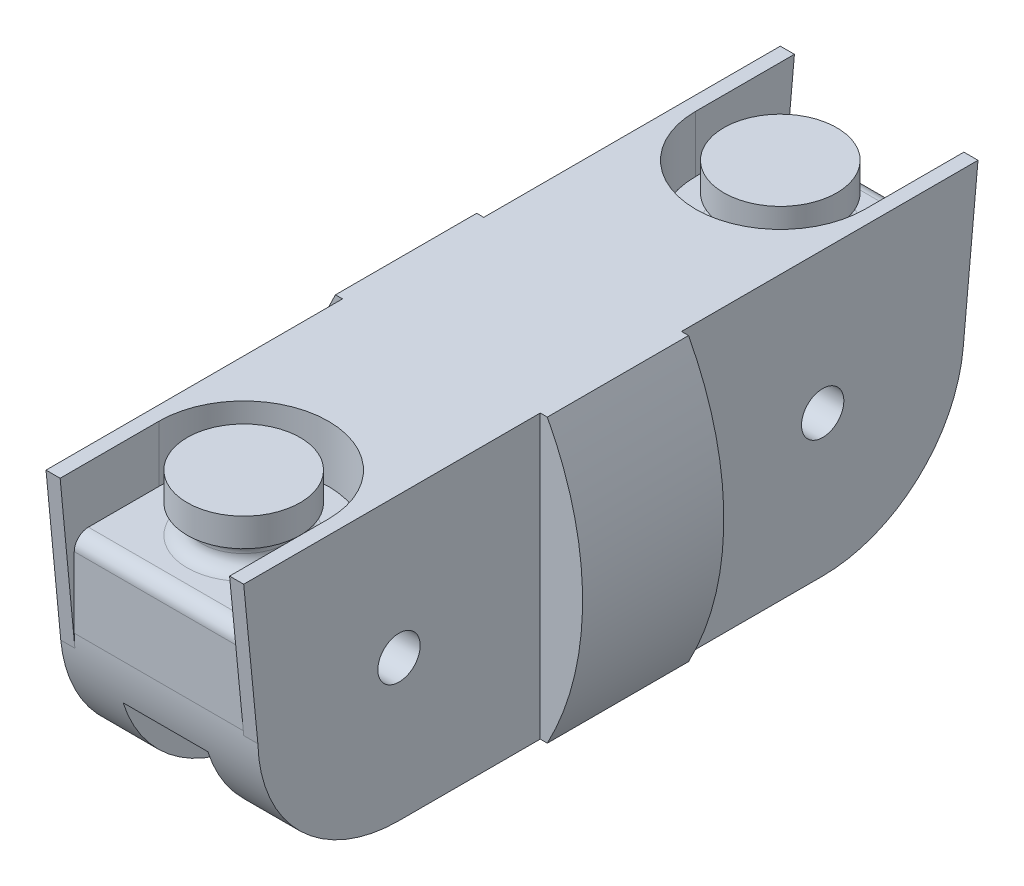
SolidWorks part; units mm, degrees
ref_plane "Alzado" through (0, 0, 0) normal (0, 0, 1) x (1, 0, 0)
ref_plane "Planta" through (0, 0, 0) normal (0, 1, 0) x (1, 0, 0)
ref_plane "Vista lateral" through (0, 0, 0) normal (1, 0, 0) x (0, 0, -1)
sketch "Croquis2" plane through (0, 0, 0) normal (0, 0, 1) x (1, 0, 0)
  line L5 (-7.5, 10) -> (7.5, 10)
  line L7 (-7.5, -10) -> (7.5, -10)
  line L9 (-7.5, 10) -> (7.5, -10) construction
  line L10 (-7.5, -10) -> (7.5, 10) construction
  arc A2 (-7.5, 10) -> (-7.5, -10) centre (11.25, 0) ccw
  arc A3 (7.5, -10) -> (7.5, 10) centre (-11.25, 0) ccw
  point P0 (0, 0)
  dimension "D1" = 15
  dimension "D2" = 20
extrude "Saliente-Extruir1" add sketch "Croquis2" along normal blind 10
sketch "Croquis3" plane through (0, 0, 0) normal (0, 0, -1) x (-1, 0, 0)
  line L0 (7.5, -10) -> (-7.5, -10) construction
  circle A0 centre (0, -7) radius 1.5
  dimension "D2" = 3
  dimension "D1" = 3
extrude "Cortar-Extruir1" cut sketch "Croquis3" against normal blind 10
sketch "Croquis4" plane through (0, 0, 0) normal (0, 0, -1) x (-1, 0, 0)
  line L0 (7.5, -10) -> (-7.5, -10) construction
  line L2 (-7, 10) -> (-7, -10)
  line L3 (-7, -10) -> (-3, -10)
  line L4 (7, 10) -> (7, -10)
  line L5 (-7, 10) -> (7, -10) construction
  line L6 (-7, -10) -> (7, 10) construction
  line L7 (-3, -3) -> (-3, -10)
  line L8 (3, -3) -> (3, -10)
  line L10 (3, -10) -> (7, -10)
  line L11 (-3, -3) -> (3, -3)
  line L13 (-7, 10) -> (7, 10)
  point P0 (0, 0)
  dimension "D1" = 14
  dimension "D2" = 4
  dimension "D3" = 4
  dimension "D4" = 7
extrude "Saliente-Extruir2" add sketch "Croquis4" along normal blind 20
sketch "Croquis5" plane through (0, 0, 10) normal (0, 0, 1) x (1, 0, 0)
  line L0 (-7.5, -10) -> (7.5, -10) construction
  line L2 (-7, 10) -> (-7, -10)
  line L3 (-7, -10) -> (-3, -10)
  line L4 (7, 10) -> (7, -10)
  line L5 (-7, 10) -> (7, -10) construction
  line L6 (-7, -10) -> (7, 10) construction
  line L7 (-3, -3) -> (-3, -10)
  line L8 (3, -3) -> (3, -10)
  line L9 (3, -10) -> (7, -10)
  line L11 (-3, -3) -> (3, -3)
  line L12 (-7, 10) -> (7, 10)
  point P0 (0, 0)
  dimension "D1" = 14
  dimension "D4" = 7
extrude "Saliente-Extruir3" add sketch "Croquis5" along normal blind 20
sketch "Croquis6" plane through (7, 0, 0) normal (1, 0, 0) x (0, 0, -1)
  line L0 (-30, -10) -> (-30, 10) construction
  line L1 (-30, -10) -> (-10, -10) construction
  line L2 (20, 10) -> (20, -10) construction
  circle A0 centre (-20, 0) radius 1.5
  circle A1 centre (10, 0) radius 1.5
  dimension "D3" = 3
  dimension "D6" = 3
  dimension "D1" = 10
  dimension "D2" = 10
  dimension "D4" = 10
extrude "Cortar-Extruir2" cut sketch "Croquis6" against normal blind 14
fillet "Redondeo1" radius 10 4 edges at (5, -10, 30) (-5, -10, 30) (5, -10, -20) (-5, -10, -20)
sketch "Sketch1" plane through (0, 10, 0) normal (0, 1, 0) x (1, 0, 0)
  line L0 (-7, 20) -> (7, 20) construction
  line L1 (7, -30) -> (-7, -30) construction
  line L4 (-6, 14) -> (-6, 20)
  line L5 (-6, 20) -> (6, 20)
  line L6 (6, 14) -> (6, 20)
  line L8 (-6, -24) -> (-6, -30)
  line L9 (-6, -30) -> (6, -30)
  line L10 (6, -24) -> (6, -30)
  arc A0 (-6, 14) -> (6, 14) centre (0, 14) ccw
  arc A1 (6, -24) -> (-6, -24) centre (0, -24) ccw
  dimension "D1" = 12
  dimension "D2" = 12
  dimension "D3" = 6
  dimension "D4" = 6
extrude "Cut-Extrude1" cut sketch "Sketch1" against normal blind 4
sketch "Sketch2" plane through (0, 6, 0) normal (0, 1, 0) x (1, 0, 0)
  line L0 (-6, -30) -> (6, -30) construction
  line L1 (6, 20) -> (-6, 20) construction
  circle A0 centre (0, 14) radius 3
  circle A1 centre (0, -24) radius 3
  dimension "D1" = 6
  dimension "D2" = 6
  dimension "D3" = 6
  dimension "D4" = 6
extrude "Boss-Extrude1" add sketch "Sketch2" along normal blind 2
sketch "Sketch3" plane through (0, 8, 0) normal (0, 1, 0) x (1, 0, 0)
  circle A0 centre (0, -24) radius 4
  circle A1 centre (0, 14) radius 4
  dimension "D1" = 8
  dimension "D2" = 8
extrude "Boss-Extrude2" add sketch "Sketch3" along normal blind 2
fillet "Fillet1" radius 1 4 edges at (0, 8, 27) (0, 6, 27) (0, 8, -11) (0, 6, -11)
fillet "Fillet2" radius 1 2 edges at (0, 6, 30) (0, 6, -20)
fillet "Fillet3" radius 1 2 edges at (-1.5, -7, 0) (-1.5, -7, 10)
sketch "Sketch4" plane through (7, 0, 0) normal (1, 0, 0) x (0, 0, -1)
  line L0 (20, 10) -> (21, 10)
  line L1 (-30, 10) -> (-31, 10)
  line L2 (-31, 10) -> (-29.8626, -1.6523)
  line L3 (-29.8626, -1.6523) -> (-30, 10)
  line L4 (21, 10) -> (19.9548, -0.9502)
  line L5 (19.9548, -0.9502) -> (20, 10)
  arc A0 (-30, 0) -> (-20, -10) centre (-20, 0) ccw construction
  arc A1 (10, -10) -> (20, 0) centre (10, 0) ccw construction
  dimension "D1" = 1
  dimension "D2" = 1
extrude "Boss-Extrude3" add sketch "Sketch4" against normal blind 1
sketch "Sketch5" plane through (-7, 0, 0) normal (-1, 0, 0) x (0, 0, 1)
  line L0 (30, 10) -> (31, 10)
  line L1 (31, 10) -> (29.9548, -0.9502)
  line L2 (29.9548, -0.9502) -> (30, 10)
  line L3 (-20, 10) -> (-21, 10)
  line L4 (-21, 10) -> (-19.9548, -0.9502)
  line L5 (-19.9548, -0.9502) -> (-20, 10)
  arc A0 (20, -10) -> (30, 0) centre (20, 0) ccw construction
  dimension "D1" = 1
  dimension "D2" = 1
extrude "Boss-Extrude4" add sketch "Sketch5" against normal blind 1
